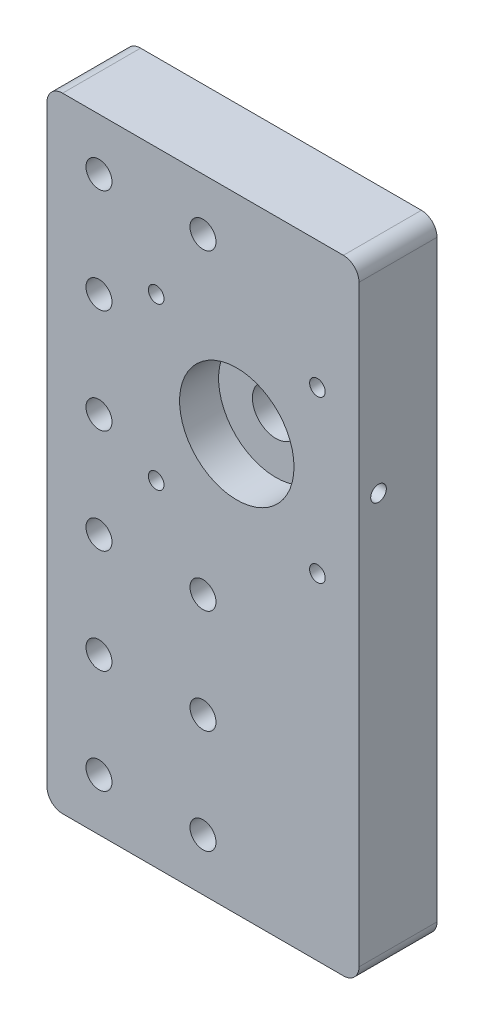
SolidWorks part; units mm, degrees
ref_plane "Płaszczyzna przednia" through (0, 0, 0) normal (0, 0, 1) x (1, 0, 0)
ref_plane "Płaszczyzna górna" through (0, 0, 0) normal (0, 1, 0) x (1, 0, 0)
ref_plane "Płaszczyzna prawa" through (0, 0, 0) normal (1, 0, 0) x (0, 0, -1)
sketch "Sketch1" plane through (0, 0, 0) normal (0, 0, 1) x (1, 0, 0)
  line L0 (72.0964, 110) -> (-17.7275, 110) construction
  line L1 (0, 0) -> (60, 0)
  line L2 (0, 0) -> (0, 120)
  line L3 (0, 120) -> (60, 120)
  line L4 (60, 0) -> (60, 120)
  line L5 (10, 111.3456) -> (10, -27.1164) construction
  line L6 (-17.7275, 10) -> (75.4304, 10) construction
  line L7 (-17.7275, 50) -> (77.7275, 50) construction
  circle A0 centre (10, 110) radius 2.5
  circle A1 centre (30, 110) radius 2.5
  circle A2 centre (10, 90) radius 2.5
  circle A3 centre (10, 70) radius 2.5
  circle A5 centre (10, 10) radius 2.5
  circle A6 centre (30, 10) radius 2.5
  circle A8 centre (30, 50) radius 2.5
  circle A9 centre (10, 50) radius 2.5
  circle A10 centre (10, 30) radius 2.5
  circle A11 centre (30, 30) radius 2.5
  dimension "D11" = 5
  dimension "D1" = 120
  dimension "D2" = 60
  dimension "D3" = 10
  dimension "D4" = 10
  dimension "D5" = 10
  dimension "D6" = 20
  dimension "D7" = 20
  dimension "D8" = 20
  dimension "D9" = 20
  dimension "D10" = 20
  dimension "D12" = 20
extrude "Boss-Extrude1" add sketch "Sketch1" along normal blind 15
fillet "Fillet1" radius 3 4 edges at (0, 0, 7.5) (60, 0, 7.5) (0, 120, 7.5) (60, 120, 7.5)
sketch "Sketch2" plane through (0, 0, 15) normal (0, 0, 1) x (1, 0, 0)
  line L0 (45.9963, 120) -> (36.5, 120) construction
  line L1 (57, 120) -> (3, 120) construction
  line L2 (36.5, 120) -> (36.5, 0) construction
  line L3 (3, 0) -> (57, 0) construction
  line L4 (0, 117) -> (0, 3) construction
  line L5 (0, 80) -> (60, 80) construction
  line L6 (60, 3) -> (60, 117) construction
  circle A0 centre (10, 70) radius 2.5 construction
  circle A1 centre (10, 90) radius 2.5 construction
  circle A2 centre (36.5, 80) radius 11
  circle A3 centre (21, 95.5) radius 1.5
  circle A4 centre (52, 95.5) radius 1.5
  circle A5 centre (52, 64.5) radius 1.5
  circle A6 centre (21, 64.5) radius 1.5
  circle A7 centre (36.5, 80) radius 4.5
  dimension "D4" = 3
  dimension "D5" = 22
  dimension "D6" = 9
  dimension "D1" = 36.5
  dimension "D2" = 31
  dimension "D3" = 31
extrude "Cut-Extrude1" cut sketch "Sketch2" against normal through all contours A7 | A4 | A3 | A5 | A6 region at (21, 95.5, 15) region at (52, 95.5, 15) region at (52, 64.5, 15) region at (36.5, 80, 15)
extrude "Cut-Extrude2" cut sketch "Sketch2<3>" against normal blind 7.5 contours A2 A7 region at (25.8111, 80, 15)
sketch "Sketch2<3>" plane through (0, 0, 15) normal (0, 0, 1) x (1, 0, 0) same geometry as "Sketch2"
sketch "Sketch3" plane through (60, 0, 0) normal (1, 0, 0) x (0, 0, -1)
  line L0 (-15, 80) -> (-7.5, 80) construction
  line L1 (-15, 3) -> (-15, 117) construction
  line L2 (-15, 91) -> (-15, 69) construction
  line L3 (-7.5, 91) -> (-7.5, 69) construction
  circle A0 centre (-11.25, 80) radius 1.5
  dimension "D1" = 3
extrude "Cut-Extrude3" cut sketch "Sketch3" against normal up to next
